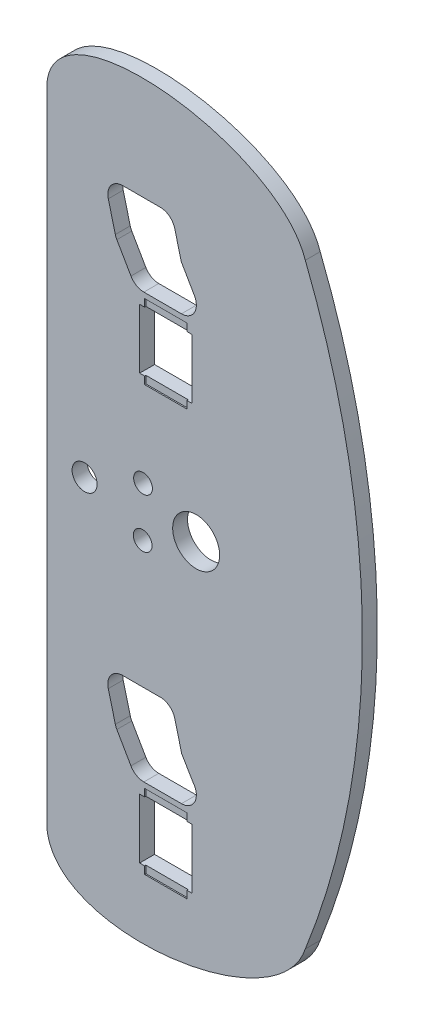
SolidWorks part; units mm, degrees
ref_plane "Front Plane" through (0, 0, 0) normal (0, 0, 1) x (1, 0, 0)
ref_plane "Top Plane" through (0, 0, 0) normal (0, 1, 0) x (1, 0, 0)
ref_plane "Right Plane" through (0, 0, 0) normal (1, 0, 0) x (0, 0, -1)
sketch "Sketch1" plane through (0, 0, 0) normal (0, 1, 0) x (1, 0, 0)
  line L0 (-92.9216, 89.0184) -> (669.0784, 89.0184)
  line L1 (669.0784, 89.0184) -> (669.0784, 419.2184)
  line L2 (-92.9216, 89.0184) -> (-92.9216, 419.2184)
  line L5 (110.2784, 495.4184) -> (465.8784, 495.4184)
  line L8 (110.2784, 495.4184) -> (-92.9216, 419.2184)
  line L9 (465.8784, 495.4184) -> (669.0784, 419.2184)
  line L10 (-92.9216, 495.4184) -> (669.0784, 495.4184) construction
sketch "Sketch2" plane through (0, 0, 0) normal (0, 0, 1) x (1, 0, 0)
  line L95 (1361.0966, 1819.7347) -> (1361.0966, 996.3635)
  arc A0 (1691.2966, 1027.0491) -> (1691.2966, 1789.0491) centre (733.0004, 1408.0491) ccw
  spline S0 degree 3 poles (1691.2966, 1027.0491) (1656.7077, 922.0591) (1371.3251, 886.2968) (1361.0966, 996.3635) knots 0 0 0 0 7.629784 7.629784 7.629784 7.629784
  spline S1 degree 3 poles (1691.2966, 1789.0491) (1656.7629, 1894.0573) (1371.3251, 1929.8013) (1361.0966, 1819.7347) knots 0 0 0 0 7.638295 7.638295 7.638295 7.638295
sketch "Sketch4" plane through (0, 0, 0) normal (0, 0, 1) x (1, 0, 0)
  line L0 (1439.599, 1189.2754) -> (1448.5991, 1154.2755)
  line L1 (1450.5414, 1149.5115) -> (1468.5414, 1118.2615)
  line L2 (1540.0357, 1006.8697) -> (1540.0357, 1016.3947)
  line L3 (1486.0607, 1097.3572) -> (1486.0607, 1006.8697) construction
  line L4 (1486.0607, 1102.1197) -> (1486.0607, 1092.5947)
  line L5 (1540.0357, 1006.8697) -> (1540.0357, 1097.3572) construction
  line L6 (1544.7982, 1102.1197) -> (1481.2982, 1102.1197) construction
  line L7 (1486.0607, 1006.8697) -> (1540.0357, 1006.8697)
  line L8 (1479.7107, 1016.3947) -> (1546.3857, 1016.3947)
  line L9 (1546.3857, 1016.3947) -> (1546.3857, 1092.5947)
  line L10 (1546.3857, 1092.5947) -> (1479.7107, 1092.5947)
  line L11 (1479.7107, 1016.3947) -> (1479.7107, 1092.5947)
  line L12 (1540.0357, 1548.8399) -> (1540.0357, 1558.3649)
  line L13 (1486.0607, 1548.8399) -> (1540.0357, 1548.8399)
  line L14 (1546.3857, 1634.5649) -> (1479.7107, 1634.5649)
  line L15 (1486.0607, 1644.0899) -> (1486.0607, 1634.5649)
  line L16 (1479.7107, 1558.3649) -> (1479.7107, 1634.5649)
  line L17 (1540.0357, 1644.0899) -> (1486.0607, 1644.0899)
  line L18 (1479.7107, 1558.3649) -> (1546.3857, 1558.3649)
  line L19 (1546.3857, 1558.3649) -> (1546.3857, 1634.5649)
  line L20 (1540.0357, 1092.5947) -> (1540.0357, 1102.1197)
  line L21 (1486.0607, 1016.3947) -> (1486.0607, 1006.8697)
  line L22 (1540.0357, 1634.5649) -> (1540.0357, 1644.0899)
  line L23 (1486.0607, 1558.3649) -> (1486.0607, 1548.8399)
  line L24 (1485.0488, 1108.7198) -> (1533.0488, 1108.7198)
  line L25 (1550.8991, 1134.423) -> (1533.383, 1164.2132)
  line L26 (1524.4986, 1198.7639) -> (1533.383, 1164.2132)
  line L27 (1459.748, 1212.9938) -> (1504.3496, 1212.9938)
  line L28 (1439.599, 1731.2456) -> (1448.5991, 1696.2457)
  line L29 (1450.5414, 1691.4817) -> (1468.5414, 1660.2317)
  line L30 (1485.0488, 1650.69) -> (1533.0488, 1650.69)
  line L31 (1549.5562, 1679.2482) -> (1532.852, 1708.2486)
  line L32 (1524.4986, 1740.7341) -> (1532.852, 1708.2486)
  line L33 (1458.0488, 1755.0399) -> (1506.0488, 1755.0399)
  line L95 (1361.0966, 1819.7347) -> (1361.0966, 996.3635)
  line L115 (1540.0357, 1102.1197) -> (1486.0607, 1102.1197)
  line L202 (1540.0357, 1097.3572) -> (1486.0607, 1097.3572) construction
  line L203 (1481.2982, 1102.1197) -> (1481.2982, 1006.8697) construction
  line L204 (1544.7982, 1006.8697) -> (1544.7982, 1102.1197) construction
  arc A0 (1691.2966, 1027.0491) -> (1691.2966, 1789.0491) centre (733.0004, 1408.0491) ccw
  arc A1 (1524.4986, 1198.7639) -> (1504.3496, 1212.9938) centre (1506.0488, 1194.0197) ccw
  arc A3 (1533.0488, 1108.7198) -> (1547.5414, 1140.1336) centre (1533.0488, 1127.7698) ccw
  arc A4 (1448.5991, 1154.2755) -> (1450.5414, 1149.5115) centre (1467.0488, 1159.0198) ccw
  arc A5 (1468.5414, 1118.2615) -> (1485.0488, 1108.7198) centre (1485.0488, 1127.7698) ccw
  arc A6 (1459.748, 1212.9938) -> (1439.599, 1189.2754) centre (1458.0488, 1194.0197) ccw
  circle A7 centre (1513.0482, 1054.4947) radius 12
  arc A8 (1524.4986, 1740.7341) -> (1506.0488, 1755.0399) centre (1506.0488, 1735.9899) ccw
  arc A10 (1533.0488, 1650.69) -> (1549.5562, 1679.2482) centre (1533.0488, 1669.74) ccw
  arc A11 (1448.5991, 1696.2457) -> (1450.5414, 1691.4817) centre (1467.0488, 1700.99) ccw
  arc A13 (1458.0488, 1755.0399) -> (1439.599, 1731.2456) centre (1458.0488, 1735.9899) ccw
  circle A15 centre (1483.5084, 1375.1967) radius 12
  circle A16 centre (1483.9827, 1438.6917) radius 12
  circle A17 centre (1551.8392, 1408.0266) radius 29.9999
  circle A18 centre (1409.3368, 1408.0266) radius 15.9995
  circle A19 centre (1513.0482, 1596.4649) radius 12
  arc A20 (1468.5414, 1660.2317) -> (1485.0488, 1650.69) centre (1485.0488, 1669.74) ccw
  arc A86 (1474.249, 1382.8299) -> (1489.0021, 1364.5282) centre (1483.5084, 1375.1967) ccw
  arc A89 (1488.8753, 1449.649) -> (1474.6166, 1431.19) centre (1483.9827, 1438.6917) ccw
  arc A97 (1557.861, 1378.6372) -> (1557.0728, 1437.5665) centre (1551.8392, 1408.0266) ccw
  arc A99 (1420.1657, 1419.8299) -> (1400.5179, 1421.402) centre (1409.3362, 1408.0491) ccw
  arc A100 (1402.6554, 1393.5084) -> (1419.641, 1395.8067) centre (1409.3362, 1408.0491) ccw
  spline S0 degree 3 poles (1691.2966, 1027.0491) (1656.7077, 922.0591) (1371.3251, 886.2968) (1361.0966, 996.3635) knots 0 0 0 0 7.629784 7.629784 7.629784 7.629784
  spline S1 degree 3 poles (1691.2966, 1789.0491) (1656.7629, 1894.0573) (1371.3251, 1929.8013) (1361.0966, 1819.7347) knots 0 0 0 0 7.638295 7.638295 7.638295 7.638295
  dimension "D1" = 4.7625
sketch "Sketch5" plane through (0, 0, 0) normal (0, 0, 1) x (1, 0, 0)
  line L0 (1361.0966, 1819.7347) -> (1361.0966, 996.3635)
  line L1 (1361.0966, 1789.0491) -> (1361.0966, 1027.0491)
  line L2 (1540.0357, 1006.8697) -> (1540.0357, 1016.3947)
  line L3 (1486.0607, 1097.3572) -> (1486.0607, 1006.8697) construction
  line L4 (1486.0607, 1102.1197) -> (1486.0607, 1092.5947)
  line L5 (1540.0357, 1006.8697) -> (1540.0357, 1097.3572) construction
  line L6 (1544.7982, 1102.1197) -> (1481.2982, 1102.1197) construction
  line L7 (1486.0607, 1006.8697) -> (1540.0357, 1006.8697)
  line L8 (1479.7107, 1016.3947) -> (1546.3857, 1016.3947)
  line L9 (1546.3857, 1016.3947) -> (1546.3857, 1092.5947)
  line L10 (1546.3857, 1092.5947) -> (1479.7107, 1092.5947)
  line L11 (1479.7107, 1016.3947) -> (1479.7107, 1092.5947)
  line L12 (1540.0357, 1548.8399) -> (1540.0357, 1558.3649)
  line L13 (1486.0607, 1548.8399) -> (1540.0357, 1548.8399)
  line L14 (1546.3857, 1634.5649) -> (1479.7107, 1634.5649)
  line L15 (1486.0607, 1644.0899) -> (1486.0607, 1634.5649)
  line L16 (1479.7107, 1558.3649) -> (1479.7107, 1634.5649)
  line L17 (1540.0357, 1644.0899) -> (1486.0607, 1644.0899)
  line L18 (1479.7107, 1558.3649) -> (1546.3857, 1558.3649)
  line L19 (1546.3857, 1558.3649) -> (1546.3857, 1634.5649)
  line L20 (1540.0357, 1092.5947) -> (1540.0357, 1102.1197)
  line L21 (1486.0607, 1016.3947) -> (1486.0607, 1006.8697)
  line L22 (1540.0357, 1634.5649) -> (1540.0357, 1644.0899)
  line L23 (1486.0607, 1558.3649) -> (1486.0607, 1548.8399)
  line L95 (1361.0966, 1819.7347) -> (1361.0966, 996.3635)
  line L115 (1540.0357, 1102.1197) -> (1486.0607, 1102.1197)
  line L199 (1363.2449, 1823.8418) -> (1361.0966, 1819.7347)
  line L200 (1361.0966, 1819.7347) -> (1361.7967, 1824.3165)
  line L201 (1361.7967, 1824.3165) -> (1363.2449, 1823.8418)
  line L202 (1540.0357, 1097.3572) -> (1486.0607, 1097.3572) construction
  line L203 (1481.2982, 1102.1197) -> (1481.2982, 1006.8697) construction
  line L204 (1544.7982, 1006.8697) -> (1544.7982, 1102.1197) construction
  arc A0 (1691.2966, 1027.0491) -> (1691.2966, 1789.0491) centre (733.0004, 1408.0491) ccw
  circle A1 centre (1506.0488, 1194.0197) radius 15.875
  circle A2 centre (1515.0488, 1159.0198) radius 15.875
  circle A3 centre (1533.0488, 1127.7698) radius 15.875
  circle A4 centre (1467.0488, 1159.0198) radius 15.875
  circle A5 centre (1485.0488, 1127.7698) radius 15.875
  circle A6 centre (1458.0488, 1194.0197) radius 15.875
  circle A7 centre (1513.0482, 1054.4947) radius 12
  circle A8 centre (1506.0488, 1735.9899) radius 15.875
  circle A9 centre (1515.0488, 1700.99) radius 15.875
  circle A10 centre (1533.0488, 1669.74) radius 15.875
  circle A11 centre (1467.0488, 1700.99) radius 15.875
  circle A12 centre (1485.0488, 1669.74) radius 15.875
  circle A13 centre (1458.0488, 1735.9899) radius 15.875
  circle A15 centre (1483.5084, 1375.1967) radius 12
  circle A16 centre (1483.9827, 1438.6917) radius 12
  circle A17 centre (1551.8392, 1408.0266) radius 29.9999
  circle A18 centre (1409.3368, 1408.0266) radius 15.9995
  circle A19 centre (1513.0482, 1596.4649) radius 12
  arc A30 (1539.4945, 1725.9331) -> (1482.0488, 1761.3623) centre (1506.0488, 1735.9899) ccw
  arc A32 (1549.9668, 1700.2938) -> (1539.4945, 1725.9331) centre (1515.0488, 1700.99) ccw
  arc A41 (1509.0488, 1644.3676) -> (1549.9668, 1700.2938) centre (1533.0488, 1669.74) ccw
  arc A46 (1450.1308, 1670.4362) -> (1509.0488, 1644.3676) centre (1485.0488, 1669.74) ccw
  arc A47 (1433.6031, 1711.0467) -> (1450.1308, 1670.4362) centre (1467.0488, 1700.99) ccw
  arc A50 (1482.0488, 1761.3623) -> (1433.6031, 1711.0467) centre (1458.0488, 1735.9899) ccw
  arc A64 (1509.0488, 1102.3974) -> (1549.9668, 1158.3235) centre (1533.0488, 1127.7698) ccw
  arc A66 (1450.1308, 1128.466) -> (1509.0488, 1102.3974) centre (1485.0488, 1127.7698) ccw
  arc A68 (1433.6031, 1169.0765) -> (1450.1308, 1128.466) centre (1467.0488, 1159.0198) ccw
  arc A70 (1539.4945, 1183.9629) -> (1482.0488, 1219.3921) centre (1506.0488, 1194.0197) ccw
  arc A72 (1549.9668, 1158.3235) -> (1539.4945, 1183.9629) centre (1515.0488, 1159.0198) ccw
  arc A73 (1482.0488, 1219.3921) -> (1433.6031, 1169.0765) centre (1458.0488, 1194.0197) ccw
  arc A86 (1474.249, 1382.8299) -> (1489.0021, 1364.5282) centre (1483.5084, 1375.1967) ccw
  arc A89 (1488.8753, 1449.649) -> (1474.6166, 1431.19) centre (1483.9827, 1438.6917) ccw
  arc A97 (1557.861, 1378.6372) -> (1557.0728, 1437.5665) centre (1551.8392, 1408.0266) ccw
  arc A99 (1420.1657, 1419.8299) -> (1400.5179, 1421.402) centre (1409.3362, 1408.0491) ccw
  arc A100 (1402.6554, 1393.5084) -> (1419.641, 1395.8067) centre (1409.3362, 1408.0491) ccw
  spline S0 degree 3 poles (1691.2966, 1027.0491) (1656.7077, 922.0591) (1371.3251, 886.2968) (1361.0966, 996.3635) knots 0 0 0 0 7.629784 7.629784 7.629784 7.629784
  spline S1 degree 3 poles (1691.2966, 1789.0491) (1656.7629, 1894.0573) (1371.3251, 1929.8013) (1361.0966, 1819.7347) knots 0 0 0 0 7.638295 7.638295 7.638295 7.638295
  dimension "D1" = 4.7625
extrude "Boss-Extrude6" add sketch "Sketch4" along normal blind 19.05 contours A0 S1 L95 S0 A15 A16 A17 A18 L33 L22 L14 L19 L18 L12 L13 L23 L16 L15 L20 L10 L9 L8 L2 L7 L21 L11 region at (1526.2742, 1873.438, 0)
extrude "Boss-Extrude7" add sketch "Sketch5" along normal blind 17.4625 contours L8 L21 L7 L2 | L4 A66 L115 | A66 L4 L10 L20 A64 L115 | L115 A64 L20 | A46 L15 L14 L22 A41 L17 | L15 A46 L17 | L17 A41 L22 | L18 L23 L13 L12 region at (1513.0482, 1011.6322, 0) region at (1509.6926, 1095.3504, 0) region at (1527.6714, 1098.1377, 0) region at (1494.6866, 1098.4222, 0) region at (1513.0482, 1553.6024, 0) region at (1509.6926, 1637.3206, 0) region at (1527.6714, 1640.1079, 0) region at (1494.6866, 1640.3924, 0)
sketch "Sketch8" plane through (0, 0, 0) normal (0, 0, 1) x (1, 0, 0)
  line L2 (1540.0357, 1006.8697) -> (1540.0357, 1016.3947)
  line L3 (1486.0607, 1097.3572) -> (1486.0607, 1006.8697) construction
  line L4 (1486.0607, 1102.1197) -> (1486.0607, 1092.5947)
  line L5 (1540.0357, 1006.8697) -> (1540.0357, 1097.3572) construction
  line L6 (1544.7982, 1102.1197) -> (1481.2982, 1102.1197) construction
  line L7 (1486.0607, 1006.8697) -> (1540.0357, 1006.8697)
  line L8 (1479.7107, 1016.3947) -> (1546.3857, 1016.3947)
  line L9 (1546.3857, 1016.3947) -> (1546.3857, 1092.5947)
  line L10 (1546.3857, 1092.5947) -> (1479.7107, 1092.5947)
  line L11 (1479.7107, 1016.3947) -> (1479.7107, 1092.5947)
  line L12 (1540.0357, 1548.8399) -> (1540.0357, 1558.3649)
  line L13 (1486.0607, 1548.8399) -> (1540.0357, 1548.8399)
  line L14 (1546.3857, 1634.5649) -> (1479.7107, 1634.5649)
  line L15 (1486.0607, 1644.0899) -> (1486.0607, 1634.5649)
  line L16 (1479.7107, 1558.3649) -> (1479.7107, 1634.5649)
  line L17 (1540.0357, 1644.0899) -> (1486.0607, 1644.0899)
  line L18 (1479.7107, 1558.3649) -> (1546.3857, 1558.3649)
  line L19 (1546.3857, 1558.3649) -> (1546.3857, 1634.5649)
  line L20 (1540.0357, 1092.5947) -> (1540.0357, 1102.1197)
  line L21 (1486.0607, 1016.3947) -> (1486.0607, 1006.8697)
  line L22 (1540.0357, 1634.5649) -> (1540.0357, 1644.0899)
  line L23 (1486.0607, 1558.3649) -> (1486.0607, 1548.8399)
  line L95 (1361.0966, 1819.7347) -> (1361.0966, 996.3635)
  line L115 (1540.0357, 1102.1197) -> (1486.0607, 1102.1197)
  line L202 (1540.0357, 1097.3572) -> (1486.0607, 1097.3572) construction
  line L203 (1481.2982, 1102.1197) -> (1481.2982, 1006.8697) construction
  line L204 (1544.7982, 1006.8697) -> (1544.7982, 1102.1197) construction
  arc A0 (1691.2966, 1027.0491) -> (1691.2966, 1789.0491) centre (733.0004, 1408.0491) ccw
  circle A1 centre (1506.0488, 1194.0197) radius 15.875
  circle A2 centre (1515.0488, 1159.0198) radius 15.875
  circle A3 centre (1533.0488, 1127.7698) radius 15.875
  circle A4 centre (1467.0488, 1159.0198) radius 15.875
  circle A5 centre (1485.0488, 1127.7698) radius 15.875
  circle A6 centre (1458.0488, 1194.0197) radius 15.875
  circle A7 centre (1513.0482, 1054.4947) radius 12
  circle A8 centre (1506.0488, 1735.9899) radius 15.875
  circle A9 centre (1515.0488, 1700.99) radius 15.875
  circle A10 centre (1533.0488, 1669.74) radius 15.875
  circle A11 centre (1467.0488, 1700.99) radius 15.875
  circle A12 centre (1485.0488, 1669.74) radius 15.875
  circle A13 centre (1458.0488, 1735.9899) radius 15.875
  circle A15 centre (1483.5084, 1375.1967) radius 12
  circle A16 centre (1483.9827, 1438.6917) radius 12
  circle A17 centre (1551.8392, 1408.0266) radius 29.9999
  circle A18 centre (1409.3368, 1408.0266) radius 15.9995
  circle A19 centre (1513.0482, 1596.4649) radius 12
  arc A30 (1539.4945, 1725.9331) -> (1482.0488, 1761.3623) centre (1506.0488, 1735.9899) ccw
  arc A32 (1549.9668, 1700.2938) -> (1539.4945, 1725.9331) centre (1515.0488, 1700.99) ccw
  arc A41 (1509.0488, 1644.3676) -> (1549.9668, 1700.2938) centre (1533.0488, 1669.74) ccw
  arc A46 (1450.1308, 1670.4362) -> (1509.0488, 1644.3676) centre (1485.0488, 1669.74) ccw
  arc A47 (1433.6031, 1711.0467) -> (1450.1308, 1670.4362) centre (1467.0488, 1700.99) ccw
  arc A50 (1482.0488, 1761.3623) -> (1433.6031, 1711.0467) centre (1458.0488, 1735.9899) ccw
  arc A64 (1509.0488, 1102.3974) -> (1549.9668, 1158.3235) centre (1533.0488, 1127.7698) ccw
  arc A66 (1450.1308, 1128.466) -> (1509.0488, 1102.3974) centre (1485.0488, 1127.7698) ccw
  arc A68 (1433.6031, 1169.0765) -> (1450.1308, 1128.466) centre (1467.0488, 1159.0198) ccw
  arc A70 (1539.4945, 1183.9629) -> (1482.0488, 1219.3921) centre (1506.0488, 1194.0197) ccw
  arc A72 (1549.9668, 1158.3235) -> (1539.4945, 1183.9629) centre (1515.0488, 1159.0198) ccw
  arc A73 (1482.0488, 1219.3921) -> (1433.6031, 1169.0765) centre (1458.0488, 1194.0197) ccw
  arc A86 (1474.249, 1382.8299) -> (1489.0021, 1364.5282) centre (1483.5084, 1375.1967) ccw
  arc A89 (1488.8753, 1449.649) -> (1474.6166, 1431.19) centre (1483.9827, 1438.6917) ccw
  arc A97 (1557.861, 1378.6372) -> (1557.0728, 1437.5665) centre (1551.8392, 1408.0266) ccw
  arc A99 (1420.1657, 1419.8299) -> (1400.5179, 1421.402) centre (1409.3362, 1408.0491) ccw
  arc A100 (1402.6554, 1393.5084) -> (1419.641, 1395.8067) centre (1409.3362, 1408.0491) ccw
  spline S0 degree 3 poles (1691.2966, 1027.0491) (1656.7077, 922.0591) (1371.3251, 886.2968) (1361.0966, 996.3635) knots 0 0 0 0 7.629784 7.629784 7.629784 7.629784
  spline S1 degree 3 poles (1691.2966, 1789.0491) (1656.7629, 1894.0573) (1371.3251, 1929.8013) (1361.0966, 1819.7347) knots 0 0 0 0 7.638295 7.638295 7.638295 7.638295
  dimension "D1" = 4.7625
sketch "Sketch9" plane through (0, 0, 0) normal (0, 0, 1) x (1, 0, 0)
  line L2 (1540.0357, 1006.8697) -> (1540.0357, 1016.3947)
  line L3 (1486.0607, 1097.3572) -> (1486.0607, 1006.8697) construction
  line L4 (1486.0607, 1102.1197) -> (1486.0607, 1092.5947)
  line L5 (1540.0357, 1006.8697) -> (1540.0357, 1097.3572) construction
  line L6 (1544.7982, 1102.1197) -> (1481.2982, 1102.1197) construction
  line L7 (1486.0607, 1006.8697) -> (1540.0357, 1006.8697)
  line L8 (1479.7107, 1016.3947) -> (1546.3857, 1016.3947)
  line L9 (1546.3857, 1016.3947) -> (1546.3857, 1092.5947)
  line L10 (1546.3857, 1092.5947) -> (1479.7107, 1092.5947)
  line L11 (1479.7107, 1016.3947) -> (1479.7107, 1092.5947)
  line L12 (1540.0357, 1548.8399) -> (1540.0357, 1558.3649)
  line L13 (1486.0607, 1548.8399) -> (1540.0357, 1548.8399)
  line L14 (1546.3857, 1634.5649) -> (1479.7107, 1634.5649)
  line L15 (1486.0607, 1644.0899) -> (1486.0607, 1634.5649)
  line L16 (1479.7107, 1558.3649) -> (1479.7107, 1634.5649)
  line L17 (1540.0357, 1644.0899) -> (1486.0607, 1644.0899)
  line L18 (1479.7107, 1558.3649) -> (1546.3857, 1558.3649)
  line L19 (1546.3857, 1558.3649) -> (1546.3857, 1634.5649)
  line L20 (1540.0357, 1092.5947) -> (1540.0357, 1102.1197)
  line L21 (1486.0607, 1016.3947) -> (1486.0607, 1006.8697)
  line L22 (1540.0357, 1634.5649) -> (1540.0357, 1644.0899)
  line L23 (1486.0607, 1558.3649) -> (1486.0607, 1548.8399)
  line L95 (1361.0966, 1819.7347) -> (1361.0966, 996.3635)
  line L115 (1540.0357, 1102.1197) -> (1486.0607, 1102.1197)
  line L202 (1540.0357, 1097.3572) -> (1486.0607, 1097.3572) construction
  line L203 (1481.2982, 1102.1197) -> (1481.2982, 1006.8697) construction
  line L204 (1544.7982, 1006.8697) -> (1544.7982, 1102.1197) construction
  arc A0 (1691.2966, 1027.0491) -> (1691.2966, 1789.0491) centre (733.0004, 1408.0491) ccw
  circle A1 centre (1506.0488, 1194.0197) radius 15.875
  circle A2 centre (1515.0488, 1159.0198) radius 15.875
  circle A3 centre (1533.0488, 1127.7698) radius 15.875
  circle A4 centre (1467.0488, 1159.0198) radius 15.875
  circle A5 centre (1485.0488, 1127.7698) radius 15.875
  circle A6 centre (1458.0488, 1194.0197) radius 15.875
  circle A7 centre (1513.0482, 1054.4947) radius 12
  circle A8 centre (1506.0488, 1735.9899) radius 15.875
  circle A9 centre (1515.0488, 1700.99) radius 15.875
  circle A10 centre (1533.0488, 1669.74) radius 15.875
  circle A11 centre (1467.0488, 1700.99) radius 15.875
  circle A12 centre (1485.0488, 1669.74) radius 15.875
  circle A13 centre (1458.0488, 1735.9899) radius 15.875
  circle A15 centre (1483.5084, 1375.1967) radius 12
  circle A16 centre (1483.9827, 1438.6917) radius 12
  circle A17 centre (1551.8392, 1408.0266) radius 29.9999
  circle A18 centre (1409.3368, 1408.0266) radius 15.9995
  circle A19 centre (1513.0482, 1596.4649) radius 12
  arc A30 (1539.4945, 1725.9331) -> (1482.0488, 1761.3623) centre (1506.0488, 1735.9899) ccw
  arc A32 (1549.9668, 1700.2938) -> (1539.4945, 1725.9331) centre (1515.0488, 1700.99) ccw
  arc A41 (1509.0488, 1644.3676) -> (1549.9668, 1700.2938) centre (1533.0488, 1669.74) ccw
  arc A46 (1450.1308, 1670.4362) -> (1509.0488, 1644.3676) centre (1485.0488, 1669.74) ccw
  arc A47 (1433.6031, 1711.0467) -> (1450.1308, 1670.4362) centre (1467.0488, 1700.99) ccw
  arc A50 (1482.0488, 1761.3623) -> (1433.6031, 1711.0467) centre (1458.0488, 1735.9899) ccw
  arc A64 (1509.0488, 1102.3974) -> (1549.9668, 1158.3235) centre (1533.0488, 1127.7698) ccw
  arc A66 (1450.1308, 1128.466) -> (1509.0488, 1102.3974) centre (1485.0488, 1127.7698) ccw
  arc A68 (1433.6031, 1169.0765) -> (1450.1308, 1128.466) centre (1467.0488, 1159.0198) ccw
  arc A70 (1539.4945, 1183.9629) -> (1482.0488, 1219.3921) centre (1506.0488, 1194.0197) ccw
  arc A72 (1549.9668, 1158.3235) -> (1539.4945, 1183.9629) centre (1515.0488, 1159.0198) ccw
  arc A73 (1482.0488, 1219.3921) -> (1433.6031, 1169.0765) centre (1458.0488, 1194.0197) ccw
  arc A86 (1474.249, 1382.8299) -> (1489.0021, 1364.5282) centre (1483.5084, 1375.1967) ccw
  arc A89 (1488.8753, 1449.649) -> (1474.6166, 1431.19) centre (1483.9827, 1438.6917) ccw
  arc A97 (1557.861, 1378.6372) -> (1557.0728, 1437.5665) centre (1551.8392, 1408.0266) ccw
  arc A99 (1420.1657, 1419.8299) -> (1400.5179, 1421.402) centre (1409.3362, 1408.0491) ccw
  arc A100 (1402.6554, 1393.5084) -> (1419.641, 1395.8067) centre (1409.3362, 1408.0491) ccw
  spline S0 degree 3 poles (1691.2966, 1027.0491) (1656.7077, 922.0591) (1371.3251, 886.2968) (1361.0966, 996.3635) knots 0 0 0 0 7.629784 7.629784 7.629784 7.629784
  spline S1 degree 3 poles (1691.2966, 1789.0491) (1656.7629, 1894.0573) (1371.3251, 1929.8013) (1361.0966, 1819.7347) knots 0 0 0 0 7.638295 7.638295 7.638295 7.638295
  dimension "D1" = 4.7625
